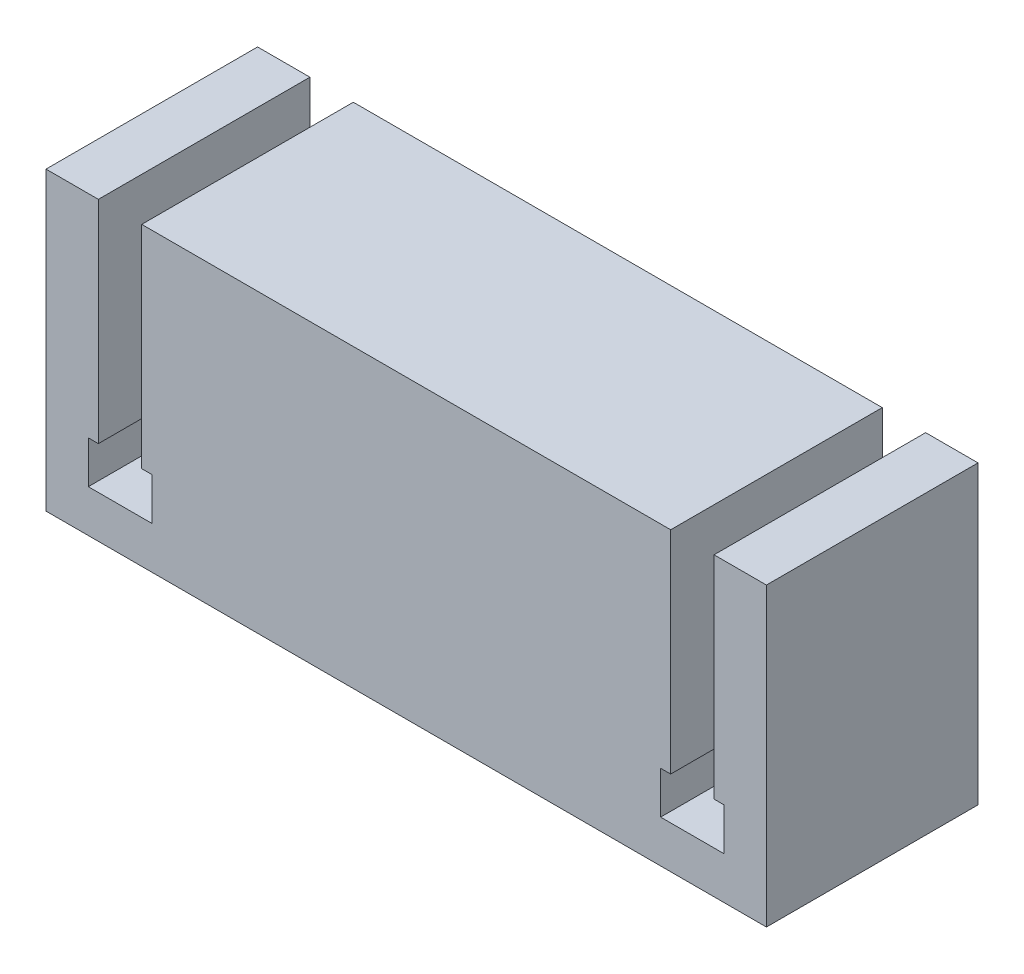
SolidWorks part; units mm, degrees
ref_plane "Front Plane" through (0, 0, 0) normal (0, 0, 1) x (1, 0, 0)
ref_plane "Top Plane" through (0, 0, 0) normal (0, 1, 0) x (1, 0, 0)
ref_plane "Right Plane" through (0, 0, 0) normal (1, 0, 0) x (0, 0, -1)
sketch "Sketch1" plane through (0, 0, 0) normal (0, 0, 1) x (1, 0, 0)
  line L0 (85.125, -35) -> (-85.125, -35)
  line L1 (-85.125, -35) -> (-85.125, 35)
  line L2 (-85.125, 35) -> (-72.75, 35)
  line L3 (-72.75, 35) -> (-72.75, -15)
  line L4 (-72.75, -15) -> (-75.125, -15)
  line L5 (-75.125, -15) -> (-75.125, -25)
  line L6 (-75.125, -25) -> (-60.125, -25)
  line L7 (-60.125, -25) -> (-60.125, -15)
  line L8 (-60.125, -15) -> (-62.5, -15)
  line L9 (-62.5, -15) -> (-62.5, 35)
  line L10 (-62.5, 35) -> (62.5, 35)
  line L11 (62.5, 35) -> (62.5, -15)
  line L12 (62.5, -15) -> (60.125, -15)
  line L13 (60.125, -15) -> (60.125, -25)
  line L14 (60.125, -25) -> (75.125, -25)
  line L15 (75.125, -25) -> (75.125, -15)
  line L16 (75.125, -15) -> (72.75, -15)
  line L17 (72.75, -15) -> (72.75, 35)
  line L18 (72.75, 35) -> (85.125, 35)
  line L19 (85.125, 35) -> (85.125, -35)
  line L20 (0, -35) -> (0, 35) construction
  dimension "D1" = 15
  dimension "D2" = 10.25
  dimension "D3" = 10
  dimension "D4" = 50
  dimension "D5" = 10
  dimension "D6" = 10
  dimension "D7" = 125
extrude "Boss-Extrude1" add sketch "Sketch1" along normal blind 25 and the other way blind 25
